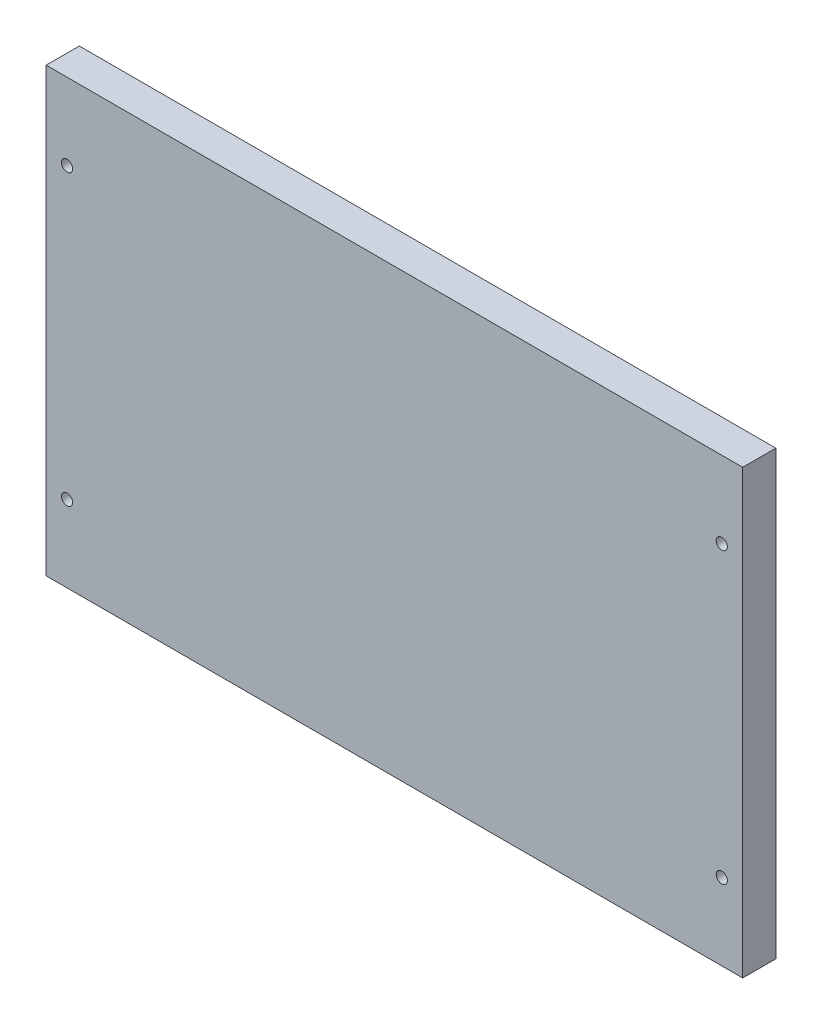
SolidWorks part; units mm, degrees
ref_plane "Front Plane" through (0, 0, 0) normal (0, 0, 1) x (1, 0, 0)
ref_plane "Top Plane" through (0, 0, 0) normal (0, 1, 0) x (1, 0, 0)
ref_plane "Right Plane" through (0, 0, 0) normal (1, 0, 0) x (0, 0, -1)
sketch "Sketch1" plane through (0, 0, 0) normal (0, 0, 1) x (1, 0, 0)
  line L1 (0, 0) -> (200, 0)
  line L2 (0, 0) -> (0, 127)
  line L3 (0, 127) -> (200, 127)
  line L4 (200, 0) -> (200, 127)
  circle A3 centre (6, 105) radius 1.6
  circle A4 centre (6, 22) radius 1.6
  circle A5 centre (194, 22) radius 1.6
  circle A6 centre (194, 105) radius 1.6
  dimension "D11" = 3.2
  dimension "D14" = 3.2
  dimension "D17" = 3.2
  dimension "D22" = 3.2
  dimension "D1" = 127
  dimension "D2" = 200
  dimension "D12" = 6
  dimension "D13" = 22
  dimension "D15" = 6
  dimension "D16" = 22
  dimension "D18" = 6
  dimension "D19" = 22
  dimension "D20" = 6
  dimension "D21" = 22
extrude "Wall" add sketch "Sketch1" along normal blind 9.525
sketch "Sketch2" [suppressed] plane through (0, 0, 6.35) normal (0, 0, 1) x (1, 0, 0)
  line L0 (100, 127) -> (100, 98.425) construction
  line L1 (200, 127) -> (0, 127) construction
  line L2 (100, 98.425) -> (66.6667, 98.425) construction
  line L3 (100, 98.425) -> (133.3333, 98.425) construction
  line L4 (0, 127) -> (0, 0) construction
  circle A0 centre (100, 98.425) radius 3.9687
  circle A1 centre (66.6667, 98.425) radius 3.9688
  circle A2 centre (133.3333, 98.425) radius 3.9687
  dimension "D2" = 7.9375
  dimension "D1" = 28.575
  dimension "D3" = 66.6667
extrude "RodSupportCutouts" [suppressed] cut sketch "Sketch2" against normal up to next
sketch "Sketch3" [suppressed] plane through (0, 0, 6.35) normal (0, 0, 1) x (1, 0, 0)
  line L1 (25.4, 88.9) -> (174.6, 88.9)
  line L2 (25.4, 88.9) -> (25.4, 114.3)
  line L3 (25.4, 114.3) -> (174.6, 114.3)
  line L4 (174.6, 88.9) -> (174.6, 114.3)
  line L5 (25.4, 88.9) -> (174.6, 114.3) construction
  line L6 (25.4, 114.3) -> (174.6, 88.9) construction
  line L7 (200, 127) -> (0, 127) construction
  line L8 (0, 127) -> (0, 0) construction
  point P0 (100, 101.6)
  point P9 (100, 127)
  dimension "D1" = 25.4
  dimension "D2" = 25.4
  dimension "D3" = 25.4
extrude "CannulaLargeCutout" [suppressed] cut sketch "Sketch3" against normal up to next
sketch "Sketch4" [suppressed] plane through (0, 0, 6.35) normal (0, 0, 1) x (1, 0, 0)
  line L0 (6, 103.5) -> (194, 103.5) construction
  line L1 (6, 105) -> (6, 22) construction
  line L2 (194, 105) -> (194, 22) construction
  line L3 (200, 127) -> (0, 127) construction
  line L4 (0, 127) -> (0, 0) construction
  circle A0 centre (60, 103.5) radius 6.35
  circle A1 centre (20, 103.5) radius 6.35
  circle A2 centre (100, 103.5) radius 6.35
  circle A3 centre (140, 103.5) radius 6.35
  circle A4 centre (60, 63.5) radius 6.35
  circle A5 centre (100, 63.5) radius 6.35
  circle A6 centre (140, 63.5) radius 6.35
  circle A7 centre (60, 23.5) radius 6.35
  circle A8 centre (100, 23.5) radius 6.35
  circle A9 centre (140, 23.5) radius 6.35
  circle A10 centre (20, 63.5) radius 6.35
  circle A11 centre (20, 23.5) radius 6.35
  circle A12 centre (180, 103.5) radius 6.35
  circle A13 centre (180, 63.5) radius 6.35
  circle A14 centre (180, 23.5) radius 6.35
  point P42 (100, 127)
  point P45 (0, 63.5)
  dimension "D3" = 12.7
  dimension "D1" = 5
  dimension "D2" = 3
extrude "CannulaHoles" [suppressed] cut sketch "Sketch4" against normal up to next
equation "\"Length\"= 283mm"
equation "\"Width\"= 225mm"
equation "\"WallThickness\"= 12.5mm"
equation "\"UpperWaterJacketThickness\"= 28mm"
equation "\"SpacerHeight\"= 80.2mm"
equation "\"SpacerCornerWidth\"= 10mm"
equation "\"SpacerCornerHeight\"= 60.16mm"
equation "\"SpacerPegDiameter\"= 10mm"
equation "\"SpacerPegHeight\"= 10mm"
equation "\"TubingShort\"= 110mm"
equation "\"TubingLong\"= 175mm"
equation "\"PlateLength\"= 252mm"
equation "\"PlateWidth\"= 190mm"
equation "\"PlateHoleDiameter\"= 5.9mm"
equation "\"PlateHoleBottom\"= 2mm"
equation "\"PlateHoleSide\"= 1.55mm"
equation "\"PlateHoleSpacing\"= 3.1mm"
equation "\"PlateThickness\"= 1.55mm"
equation "\"ReservoirBottom\"= 12.5mm"
equation "\"ReservoirSupportWidth\"= 12mm"
equation "\"ReservoirSupportHeight\"= 15.1mm"
equation "\"ReservoirSupportPlacementHeight\"= 50mm"
equation "\"ReservoirHoleDiameter\"= 12.7mm"
equation "\"ReservoirHoleRight\"= 25mm"
equation "\"ReservoirHoleTop\"= \"ReservoirSupportPlacementHeight\""
equation "\"ReservoirHeight\"= 90mm"
equation "\"ReservoirPortBottom\"= 4mm"
equation "\"ReservoirPortTop\"= 10mm"
equation "\"ReservoirPortWidth\"= 101mm"
equation "\"CustomSpacerWallThickness\"= 0.375in"
equation "\"CustomSpacerHeight\"= 5in"
equation "\"CustomSpacerRodHoleHeight\"= .75in"
equation "\"CustomSpacerRodHoleDiameter\"= .3125in"
equation "\"ScrewBlockSide\"= 12mm"
equation "\"ScrewBlockUpperHeight\"= 16mm"
equation "\"ScrewBlockLowerHeight\"= 16mm"
equation "\"InternalLength\"= \"Length\" - ( 2 * \"WallThickness\" )"
equation "\"InternalWidth\"= \"Width\" - ( 2 * \"WallThickness\" )"
equation "\"CustomSpacerPegHeight\"= 1in"
equation "\"CustomSpacerScrewBore\"=3.2mm"
equation "\"CustomSpacerScrewDepth\"=10mm"
equation "\"D1@Sketch1\"=\"CustomSpacerHeight\""
equation "\"D2@Sketch1\"=\"InternalWidth\""
equation "\"D11@Sketch1\"=\"CustomSpacerScrewBore\""
equation "\"D12@Sketch1\"=\"ScrewBlockSide\"/2"
equation "\"D13@Sketch1\"=\"ScrewBlockUpperHeight\"+\"ScrewBlockSide\"/2"
equation "\"D14@Sketch1\"=\"CustomSpacerScrewBore\""
equation "\"D15@Sketch1\"=\"ScrewBlockSide\"/2"
equation "\"D16@Sketch1\"=\"ScrewBlockLowerHeight\"+\"ScrewBlockSide\"/2"
equation "\"D17@Sketch1\"=\"CustomSpacerScrewBore\""
equation "\"D18@Sketch1\"=\"ScrewBlockSide\"/2"
equation "\"D19@Sketch1\"=\"ScrewBlockUpperHeight\"+\"ScrewBlockSide\"/2"
equation "\"D20@Sketch1\"=\"ScrewBlockSide\"/2"
equation "\"D21@Sketch1\"=\"ScrewBlockLowerHeight\"+\"ScrewBlockSide\"/2"
equation "\"D22@Sketch1\"=\"CustomSpacerScrewBore\""
equation "\"D1@Wall\" = \"CustomSpacerWallThickness\""
equation "\"D1@Sketch2\"=\"CustomSpacerRodHoleHeight\" + \"CustomSpacerRodHoleDiameter\" +0.0625in"
equation "\"D2@Sketch2\"=\"CustomSpacerRodHoleDiameter\""
equation "\"D3@Sketch2\"=\"InternalWidth\" / 3"
equation "\"D1@Sketch3\"=1in"
